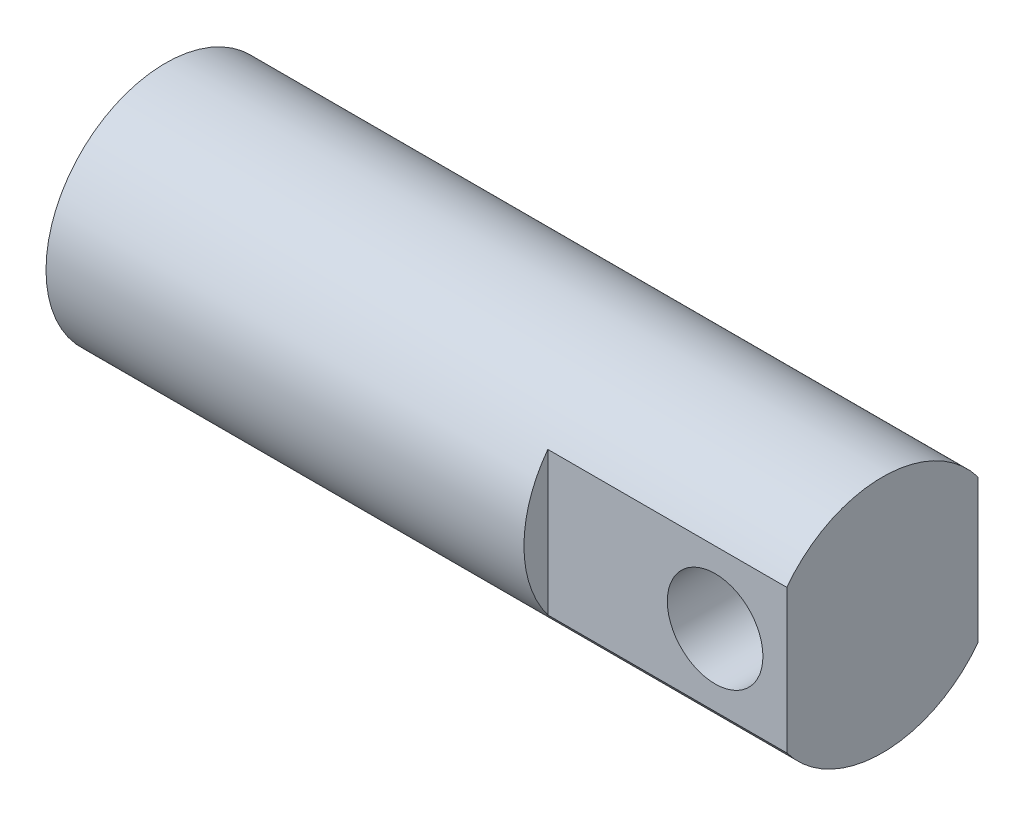
SolidWorks part; units mm, degrees
material "201 Annealed Stainless Steel (SS)"
ref_plane "Front Plane" through (0, 0, 0) normal (0, 0, 1) x (1, 0, 0)
ref_plane "Top Plane" through (0, 0, 0) normal (0, 1, 0) x (1, 0, 0)
ref_plane "Right Plane" through (0, 0, 0) normal (1, 0, 0) x (0, 0, -1)
sketch "Sketch1" plane through (0, 0, 0) normal (0, 0, 1) x (1, 0, 0)
  line L0 (-15, 0) -> (15, 0) construction
  line L1 (-15, 0) -> (15, 0)
  line L2 (-15, 0) -> (-15, 5)
  line L3 (-15, 5) -> (15, 5)
  line L4 (15, 0) -> (15, 5)
  line L5 (-15, -5) -> (15, 5) construction
  line L6 (-15, 5) -> (15, -5) construction
  point P0 (0, 0)
  dimension "D1" = 5
  dimension "D2" = 30
revolve "Revolve1" add sketch "Sketch1" angle 360 about L1
sketch "Sketch2" plane through (0, 0, 0) normal (0, 0, 1) x (1, 0, 0)
  line L0 (15, -5) -> (15, 5) construction
  circle A0 centre (12, 0) radius 2
  dimension "D1" = 4
  dimension "D2" = 3
extrude "Cut-Extrude1" cut sketch "Sketch2" against normal blind 10 and the other way blind 10
sketch "Sketch3" plane through (0, 0, 0) normal (0, 1, 0) x (1, 0, 0)
  line L1 (15, 5) -> (5, 5)
  line L2 (15, 5) -> (15, 4)
  line L3 (15, 4) -> (5, 4)
  line L4 (5, 5) -> (5, 4)
  line L5 (15, -5) -> (5, -5)
  line L6 (15, -5) -> (15, -4)
  line L7 (15, -4) -> (5, -4)
  line L8 (5, -5) -> (5, -4)
  dimension "D1" = 10
  dimension "D2" = 1
extrude "Cut-Extrude2" cut sketch "Sketch3" against normal blind 10 and the other way blind 10
